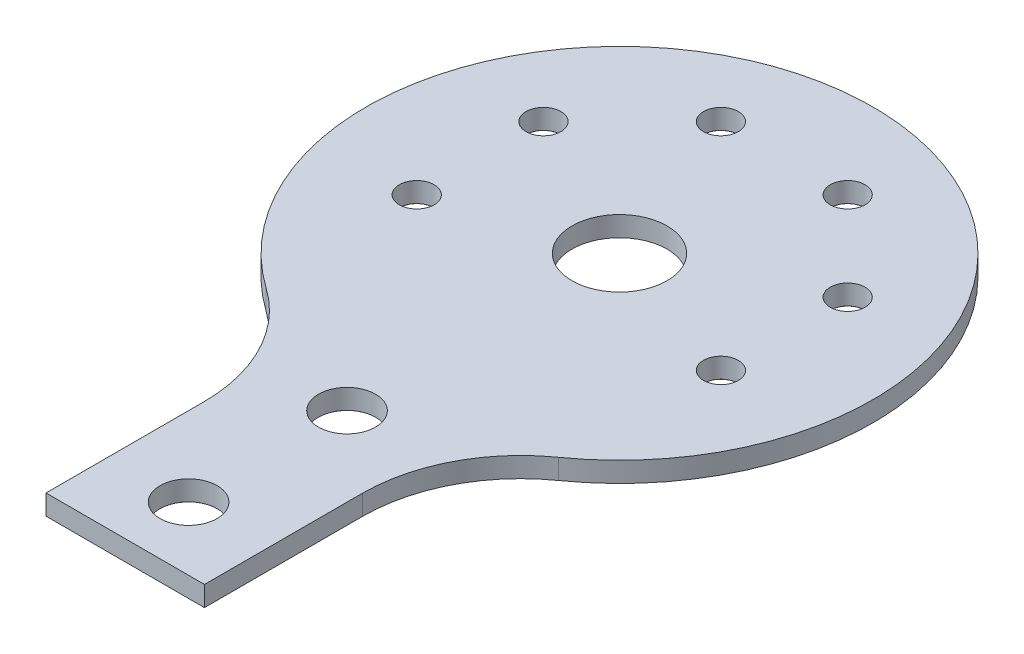
SolidWorks part; units mm, degrees
material "1060 Alloy"
ref_plane "Front Plane" through (0, 0, 0) normal (0, 0, 1) x (1, 0, 0)
ref_plane "Top Plane" through (0, 0, 0) normal (0, 1, 0) x (1, 0, 0)
ref_plane "Right Plane" through (0, 0, 0) normal (1, 0, 0) x (0, 0, -1)
sketch "Sketch1" plane through (0, 0, 0) normal (0, 1, 0) x (1, 0, 0)
  line L0 (-12.5, -77.9967) -> (12.5, -77.9967)
  line L1 (12.5, -77.9967) -> (12.5, -37.9967)
  line L2 (-12.5, -77.9967) -> (-12.5, -37.9967)
  arc A0 (12.5, -37.9967) -> (-12.5, -37.9967) centre (0, 0) ccw
  point P5 (0, -77.9967)
  dimension "D2" = 80
  dimension "D1" = 25
  dimension "D3" = 40
extrude "Boss-Extrude1" add sketch "Sketch1" along normal blind 3.175 contours A0 L2 L0 L1
sketch "Sketch2" plane through (0, 0, 0) normal (0, -1, 0) x (1, 0, 0)
  line L0 (0, -1.7463) -> (0, 1.7463) construction
  point P0 (-10, -26)
  point P1 (-24, -12)
  point P4 (-24, 8)
  point P5 (0, 0)
  point P15 (24, 8)
  point P17 (24, -12)
  point P18 (10, -26)
  dimension "D2" = 26
  dimension "D1" = 8
  dimension "D3" = 10
  dimension "D4" = 24
  dimension "D5" = 20
sketch "Sketch5" plane through (0, 0, 0) normal (0, -1, 0) x (1, 0, 0)
  circle A0 centre (0, 0) radius 7.5
  dimension "D1" = 15
extrude "Cut-Extrude1" cut sketch "Sketch5" against normal through all
sketch "Sketch6" plane through (0, 0, 0) normal (0, -1, 0) x (1, 0, 0)
  line L0 (0, 77.9967) -> (0, 42.9967) construction
  line L1 (-12.5, 77.9967) -> (12.5, 77.9967) construction
  point P5 (0, 67.9967)
  dimension "D1" = 25
  dimension "D2" = 10
hole_wizard "M8 Clearance Hole1" positions "Sketch7" profile "Sketch8" hole size "M8" standard "ANSI Metric" end condition through all
sketch "Sketch7" plane through (0, 0, 0) normal (0, -1, 0) x (-1, 0, 0)
  point P0 (0, -42.9967)
  point P3 (0, -67.9967)
sketch "Sketch8" plane through (0, 0, 42.9967) normal (1, 0, 0) x (0, 0, -1)
  line L0 (0, 0) -> (0, 3.175)
  line L1 (0, 3.175) -> (4.5, 3.175)
  line L2 (4.5, 3.175) -> (4.5, 0.025)
  line L3 (4.5, 0.025) -> (4.525, 0)
  line L5 (4.525, 0) -> (0, 0)
  line L6 (-4.5, 0.025) -> (-4.525, 0) construction
  line L11 (0, -6.35) -> (0, 107.95) construction
  dimension "Thru Hole Dia." = 9
  dimension "Thru Hole Depth" = 3.175
  dimension "Near C'Sink Dia." = 9.05
  dimension "Near C'Sink Angle" = 90
fillet "Fillet1" radius 25 2 edges at (-12.5, 1.5875, 37.9967) (12.5, 1.5875, 37.9967)
hole_wizard "M5 Clearance Hole1" positions "Sketch9" profile "Sketch10" hole size "M5" standard "ANSI Metric" end condition through all
sketch "Sketch9" plane through (0, 0, 0) normal (0, -1, 0) x (-1, 0, 0)
  point P0 (10, 26)
  point P3 (24, 12)
  point P6 (24, -8)
  point P9 (-10, 26)
  point P12 (-24, 12)
  point P15 (-24, -8)
sketch "Sketch10" plane through (-10, 0, -26) normal (1, 0, 0) x (0, 0, -1)
  line L0 (0, 0) -> (0, 3.175)
  line L1 (0, 3.175) -> (2.75, 3.175)
  line L2 (2.75, 3.175) -> (2.75, 0.025)
  line L3 (2.75, 0.025) -> (2.775, 0)
  line L5 (2.775, 0) -> (0, 0)
  line L6 (-2.75, 0.025) -> (-2.775, 0) construction
  line L11 (0, -6.35) -> (0, 107.95) construction
  dimension "Thru Hole Dia." = 5.5
  dimension "Thru Hole Depth" = 3.175
  dimension "Near C'Sink Dia." = 5.55
  dimension "Near C'Sink Angle" = 90
